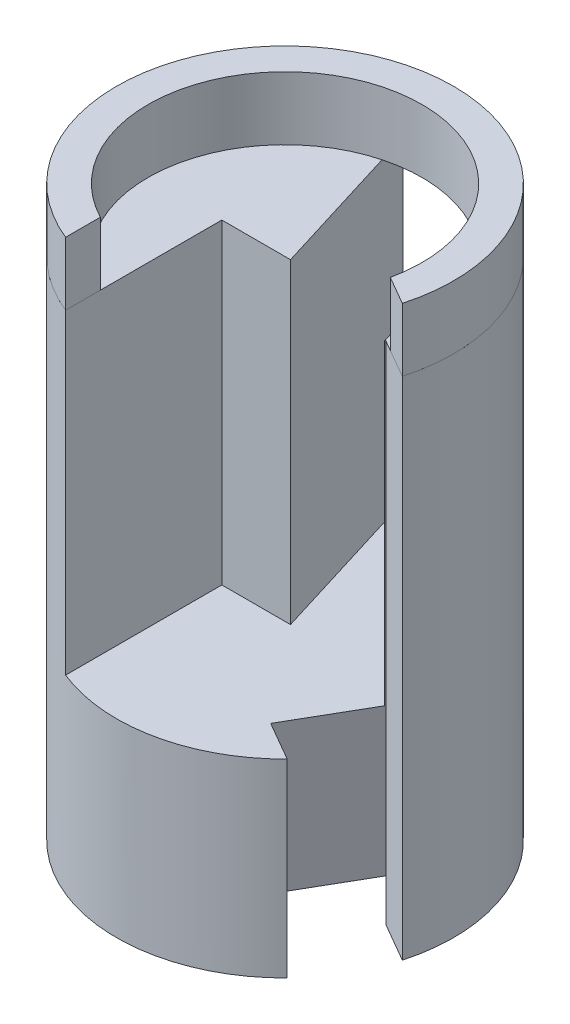
SolidWorks part; units mm, degrees
ref_plane "Front Plane" through (0, 0, 0) normal (0, 0, 1) x (1, 0, 0)
ref_plane "Top Plane" through (0, 0, 0) normal (0, 1, 0) x (1, 0, 0)
ref_plane "Right Plane" through (0, 0, 0) normal (1, 0, 0) x (0, 0, -1)
sketch "Sketch2" plane through (0, 0, 0) normal (0, 1, 0) x (1, 0, 0)
  circle A0 centre (0, 0) radius 101.6
  dimension "D1" = 203.2
extrude "Boss-Extrude1" add sketch "Sketch2" along normal blind 304.8
sketch "Sketch3" plane through (0, 304.8, 0) normal (0, 1, 0) x (1, 0, 0)
  circle A0 centre (0, 0) radius 82.55
  circle A1 centre (0, 0) radius 101.6 construction
  circle A2 centre (0, 0) radius 101.6
  dimension "D1" = 165.1
extrude "Boss-Extrude2" add sketch "Sketch3" along normal blind 38.1 separate body
sketch "Sketch4" plane through (0, 342.9, 0) normal (0, 1, 0) x (1, 0, 0)
  line L1 (-38.1, 0) -> (38.1, 0)
  line L2 (-38.1, 0) -> (-38.1, -101.6)
  line L3 (-38.1, -101.6) -> (38.1, -101.6)
  line L4 (38.1, 0) -> (38.1, -101.6)
  line L8 (-26.8987, 98.0249) -> (32.9028, -96.176)
  line L9 (-26.8987, 98.0249) -> (33.7891, 116.7129)
  line L10 (32.9028, -96.176) -> (93.5906, -77.488)
  line L11 (33.7891, 116.7129) -> (93.5906, -77.488)
  line L12 (3.4452, 107.3689) -> (63.2467, -86.832) construction
  line L13 (0, 0) -> (0, 101.6) construction
  circle A0 centre (0, 0) radius 101.6 construction
  point P4 (0, 0)
  circle M5 centre (0, 0) radius 101.6
  circle M6 centre (0, 0) radius 82.55
  dimension "D1" = 76.2
  dimension "D2" = 63.5
  dimension "D3" = 203.2
  dimension "D4" = 17.116
  dimension "D5" = 6.7193
extrude "Cut-Extrude1" cut sketch "Sketch4" against normal blind 228.6 contours L8 L1 L2 M6 | L8 L2 M6 M5 | L8 L4 M6 M5 | L1 L8 L4 M6 region at (-10.3974, 342.9, 43.1779) region at (25.5191, 342.9, 31.5319) region at (-4.199, 342.9, 89.8865) region at (33.9537, 342.9, 84.3011)
extrude "Cut-Extrude2" cut sketch "Sketch4<4>" against normal blind 190.5 from offset 38.1 contours L11 L4 M6 M5 | L11 L8 L1 L4 M6 | L11 L8 M5 M6 region at (32.4275, 342.9, -19.3523) region at (11.1293, 342.9, -88.9086) region at (62.6882, 342.9, 64.9023) offset against normal yes
sketch "Sketch4<4>" plane through (0, 342.9, 0) normal (0, 1, 0) x (1, 0, 0) same geometry as "Sketch4"
sketch "Sketch5" plane through (0, 0, 0) normal (0, -1, 0) x (1, 0, 0)
  circle A0 centre (0, 0) radius 76.2
  circle A1 centre (0, 0) radius 101.6
  circle A2 centre (0, 0) radius 101.6
  dimension "D1" = 0
  dimension "D2" = 25.4
extrude "Cut-Extrude3" cut sketch "Sketch5" against normal blind 25.4 contours A0
sketch "Sketch6" plane through (0, 342.9, 0) normal (0, 1, 0) x (1, 0, 0)
  line L0 (0, 0) -> (87.9882, -50.8) construction
  line L5 (0, 0) -> (0, -101.6) construction
  line L6 (48.8917, -57.557) -> (74.2917, -13.563)
  line L7 (74.2917, -13.563) -> (107.2873, -32.613)
  line L8 (107.2873, -32.613) -> (60.2973, -114.002)
  line L13 (60.2973, -114.002) -> (14.1554, -87.362)
  line L14 (14.1554, -87.362) -> (35.7454, -49.967)
  line L15 (35.7454, -49.967) -> (48.8917, -57.557)
  line L16 (48.8917, -57.557) -> (81.8873, -76.607)
  arc A0 (38.1, -94.1857) -> (-38.1, -94.1857) centre (0, 0) ccw construction
  arc A1 (-38.1, -94.1857) -> (86.26, -53.6822) centre (0, 0) ccw construction
  point P3 (61.5917, -35.56)
  arc M13 (-38.1, -73.2318) -> (38.1, -73.2318) centre (0, 0) cw
  arc M15 (38.1, -94.1857) -> (-38.1, -94.1857) centre (0, 0) ccw
  dimension "D1" = 25.4
  dimension "D2" = 30.48
  dimension "D3" = 60
  dimension "D4" = 38.1
  dimension "D5" = 53.28
  dimension "D6" = 43.18
extrude "Cut-Extrude4" cut sketch "Sketch6" against normal up to surface (228.6 mm away) contours L15 L6 L7 L8 L13 L14 up to face at (5.9007, 114.3, -4.3704)
extrude "Cut-Extrude5" cut sketch "Sketch6<4>" against normal through all contours L16 L8 L7 M15 | L16 L7 M13 M15 | L6 L16 L7 M13 region at (66.0294, 342.9, 38.1221) region at (78.6932, 342.9, 45.4335) region at (90.7792, 342.9, 52.4114)
sketch "Sketch6<4>" plane through (0, 342.9, 0) normal (0, 1, 0) x (1, 0, 0) same geometry as "Sketch6"
